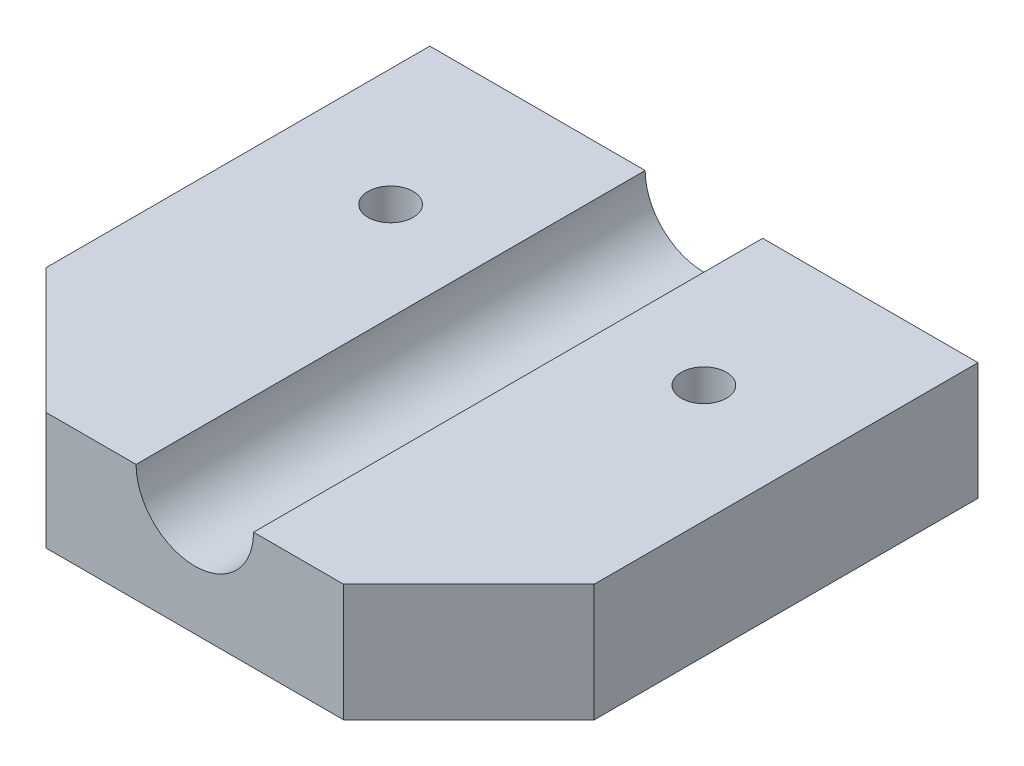
SolidWorks part; units mm, degrees
material "Nylon 6/10"
ref_plane "Front Plane" through (0, 0, 0) normal (0, 0, 1) x (1, 0, 0)
ref_plane "Top Plane" through (0, 0, 0) normal (0, 1, 0) x (1, 0, 0)
ref_plane "Right Plane" through (0, 0, 0) normal (1, 0, 0) x (0, 0, -1)
sketch "Sketch1" plane through (0, 0, 0) normal (0, 1, 0) x (1, 0, 0)
  line L1 (-22.225, -20.6375) -> (22.225, -20.6375)
  line L2 (-22.225, -20.6375) -> (-22.225, 20.6375)
  line L3 (-22.225, 20.6375) -> (22.225, 20.6375)
  line L4 (22.225, -20.6375) -> (22.225, 20.6375)
  line L5 (-22.225, -20.6375) -> (22.225, 20.6375) construction
  line L6 (-22.225, 20.6375) -> (22.225, -20.6375) construction
  point P0 (0, 0)
  dimension "D1" = 41.275
  dimension "D2" = 44.45
extrude "Boss-Extrude1" add sketch "Sketch1" along normal blind 9.525
sketch "Sketch4" plane through (0, 0, 20.6375) normal (0, 0, 1) x (1, 0, 0)
  line L0 (-22.225, 9.525) -> (22.225, 9.525) construction
  circle A0 centre (0, 9.525) radius 4.7625
  dimension "D1" = 9.525
extrude "Cut-Extrude1" cut sketch "Sketch4" against normal through all
hole_wizard "MotorHoles" positions "Sketch3" profile "Sketch2" tap size "#4-40" standard "ANSI Inch"
sketch "Sketch3" plane through (0, 0, 0) normal (0, -1, 0) x (-1, 0, 0)
  line L0 (22.225, -20.6375) -> (-22.225, -20.6375) construction
  line L2 (0, 0) -> (0, -31.1437) construction
  point P0 (-5.715, -17.4625)
  point P2 (5.715, -17.4625)
  dimension "D1" = 3.175
  dimension "D2" = 11.43
cosmetic thread "Hole Thread1" parameters "D2"=2.8448
cosmetic thread "Hole Thread2" parameters "D2"=2.8448
sketch "Sketch2" plane through (5.715, 0, 17.4625) normal (1, 0, 0) x (0, 0, -1)
  line L0 (0, 0) -> (0, 8.2992)
  line L1 (0, 8.2992) -> (1.1303, 7.62)
  line L2 (1.1303, 7.62) -> (1.1303, 0)
  line L5 (1.1303, 0) -> (0, 0)
  line L10 (0, 8.2992) -> (-1.1303, 7.62) construction
  line L11 (0, -6.35) -> (0, 107.95) construction
  dimension "Tap Drill Dia." = 2.2606
  dimension "Tap Drill Depth" = 7.62
  dimension "Drill Angle" = 118
hole_wizard "CBORE for #6 Socket Head Cap Screw1" positions "Sketch6" profile "Sketch5" counterbore size "#6" standard "ANSI Inch" end condition through all
sketch "Sketch6" plane through (0, 0, 0) normal (0, -1, 0) x (-1, 0, 0)
  line L0 (0, 0) -> (0, 20.3228) construction
  line L2 (-22.225, 20.6375) -> (22.225, 20.6375) construction
  point P0 (-12.7, 7.9375)
  point P2 (12.7, 7.9375)
  dimension "D1" = 25.4
  dimension "D2" = 12.7
sketch "Sketch5" plane through (12.7, 0, -7.9375) normal (1, 0, 0) x (0, 0, -1)
  line L0 (0, 0) -> (0, 9.525)
  line L1 (0, 9.525) -> (1.8288, 9.525)
  line L3 (1.8288, 9.525) -> (1.8288, 3.5052)
  line L4 (3.5725, 3.5052) -> (1.8288, 3.5052)
  line L5 (3.5725, 3.5052) -> (3.5725, 0.635)
  line L6 (3.5725, 0.635) -> (4.2075, 0)
  line L7 (4.2075, 0) -> (0, 0)
  line L8 (-3.5725, 0.635) -> (-4.2075, 0) construction
  line L11 (0, -6.35) -> (0, 107.95) construction
  dimension "Thru Hole Dia." = 3.6576
  dimension "Thru Hole Depth" = 9.525
  dimension "C'Bore Dia." = 7.145
  dimension "C'Bore Depth" = 3.5052
  dimension "Near C'Sink Dia." = 8.415
  dimension "Near C'Sink Angle" = 90
chamfer "Chamfer1" distance 10.16 angle 45 2 edges at (22.225, 4.7625, 20.6375) (-22.225, 4.7625, 20.6375)
